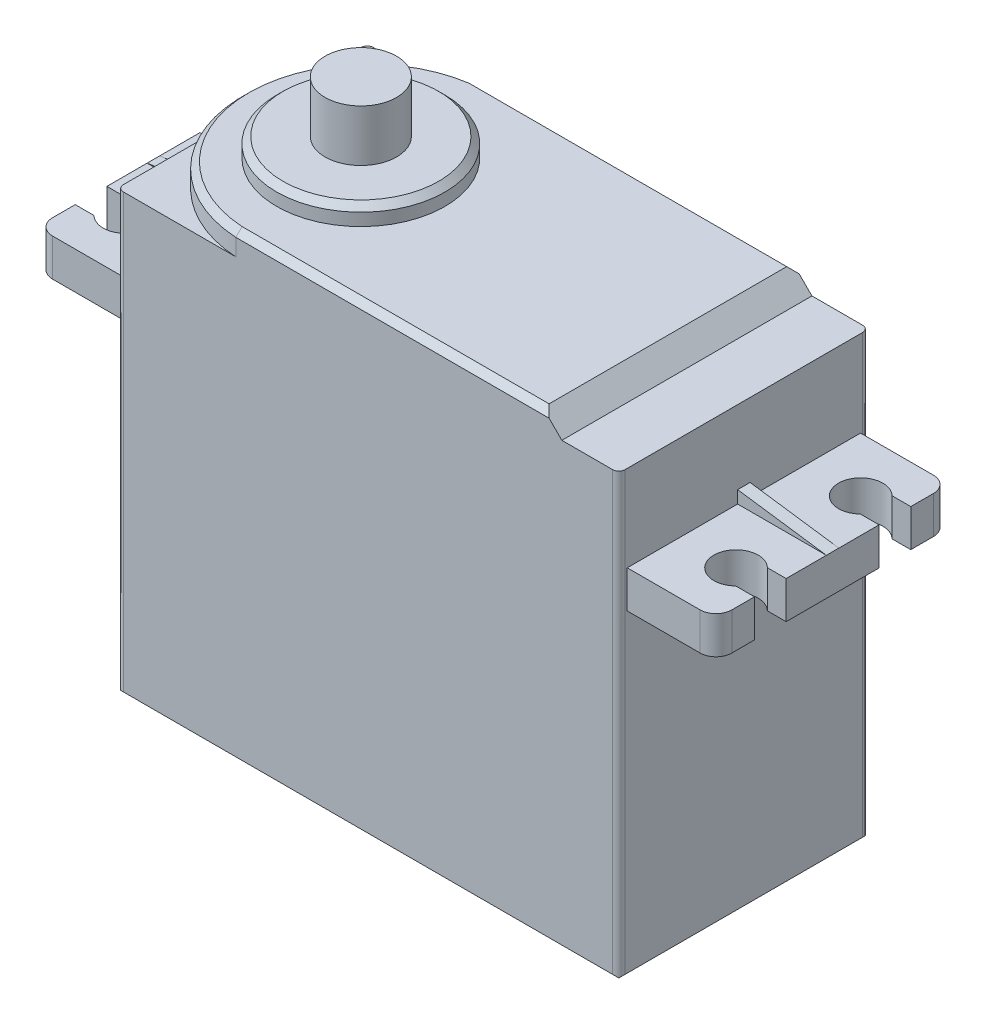
SolidWorks part; units mm, degrees
ref_plane "Front Plane" through (0, 0, 0) normal (0, 0, 1) x (1, 0, 0)
ref_plane "Top Plane" through (0, 0, 0) normal (0, 1, 0) x (1, 0, 0)
ref_plane "Right Plane" through (0, 0, 0) normal (1, 0, 0) x (0, 0, -1)
sketch "Sketch1" plane through (0, 0, 0) normal (0, 1, 0) x (1, 0, 0)
  line L1 (-20.1295, -10.033) -> (20.1295, -10.033)
  line L2 (-20.1295, -10.033) -> (-20.1295, 10.033)
  line L3 (-20.1295, 10.033) -> (20.1295, 10.033)
  line L4 (20.1295, -10.033) -> (20.1295, 10.033)
  line L5 (-20.1295, -10.033) -> (20.1295, 10.033) construction
  line L6 (-20.1295, 10.033) -> (20.1295, -10.033) construction
  point P0 (0, 0)
  dimension "D1" = 20.066
  dimension "D2" = 40.259
extrude "Boss-Extrude1" add sketch "Sketch1" along normal blind 38.1
ref_plane "Plane1" through (0, 26.67, 0) normal (0, -1, 0) x (-1, 0, 0)
sketch "Sketch2" plane through (0, 26.67, 0) normal (0, -1, 0) x (-1, 0, 0)
  line L1 (27.25, -9.3599) -> (-27.25, -9.3599)
  line L2 (27.25, -9.3599) -> (27.25, 9.3599)
  line L3 (27.25, 9.3599) -> (-27.25, 9.3599)
  line L4 (-27.25, -9.3599) -> (-27.25, 9.3599)
  line L5 (27.25, -9.3599) -> (-27.25, 9.3599) construction
  line L6 (27.25, 9.3599) -> (-27.25, -9.3599) construction
  point P0 (0, 0)
  dimension "D1" = 18.7198
  dimension "D2" = 54.5
extrude "Boss-Extrude2" add sketch "Sketch2" against normal blind 2.9972
sketch "Sketch3" plane through (0, 38.1, 0) normal (0, 1, 0) x (1, 0, 0)
  line L0 (-20.1295, 10.033) -> (-20.1295, -10.033) construction
  circle A0 centre (-10.6045, 0) radius 2.8702
  dimension "D2" = 5.7404
  dimension "D1" = 9.525
extrude "Boss-Extrude3" add sketch "Sketch3" along normal blind 5.6388
sketch "Sketch4" plane through (0, 29.6672, 0) normal (0, 1, 0) x (1, 0, 0)
  line L0 (-35.4024, 0) -> (37.6199, 0) construction
  line L1 (0, 17.908) -> (0, -16.6827) construction
  circle A0 centre (-24.5, 5) radius 1.778
  circle A1 centre (-24.5, -5) radius 1.778
  circle A2 centre (24.5, -5) radius 1.778
  circle A3 centre (24.5, 5) radius 1.778
  dimension "D3" = 3.556
  dimension "D4" = 3.556
  dimension "D5" = 3.556
  dimension "D6" = 3.556
  dimension "D1" = 49
  dimension "D2" = 10
extrude "Cut-Extrude1" cut sketch "Sketch4" against normal through all
sketch "Sketch5" plane through (0, 29.6672, 0) normal (0, 1, 0) x (1, 0, 0)
  line L0 (-24.5, -5) -> (-36.94, -5) construction
  line L1 (24.5, 5) -> (34.8628, 5) construction
  line L2 (-24.5, 5) -> (-37.4141, 5) construction
  line L3 (24.5, -5) -> (35.3369, -5) construction
  line L5 (-32.12, 3.73) -> (-24.5, 3.73)
  line L6 (-32.12, 3.73) -> (-32.12, 6.27)
  line L7 (-32.12, 6.27) -> (-24.5, 6.27)
  line L8 (-24.5, 3.73) -> (-24.5, 6.27)
  line L9 (-32.12, 3.73) -> (-24.5, 6.27) construction
  line L10 (-32.12, 6.27) -> (-24.5, 3.73) construction
  line L11 (-30.85, -6.27) -> (-24.5, -6.27)
  line L12 (-30.85, -6.27) -> (-30.85, -3.73)
  line L13 (-30.85, -3.73) -> (-24.5, -3.73)
  line L14 (-24.5, -6.27) -> (-24.5, -3.73)
  line L15 (-30.85, -6.27) -> (-24.5, -3.73) construction
  line L16 (-30.85, -3.73) -> (-24.5, -6.27) construction
  line L17 (30.85, 3.73) -> (24.5, 3.73)
  line L18 (30.85, 3.73) -> (30.85, 6.27)
  line L19 (30.85, 6.27) -> (24.5, 6.27)
  line L20 (24.5, 3.73) -> (24.5, 6.27)
  line L21 (30.85, 3.73) -> (24.5, 6.27) construction
  line L22 (30.85, 6.27) -> (24.5, 3.73) construction
  line L23 (30.85, -6.27) -> (24.5, -6.27)
  line L24 (30.85, -6.27) -> (30.85, -3.73)
  line L25 (30.85, -3.73) -> (24.5, -3.73)
  line L26 (24.5, -6.27) -> (24.5, -3.73)
  line L27 (30.85, -6.27) -> (24.5, -3.73) construction
  line L28 (30.85, -3.73) -> (24.5, -6.27) construction
  point P2 (-28.31, 5)
  point P17 (-27.675, -5)
  point P22 (27.675, 5)
  point P27 (27.675, -5)
  dimension "D1" = 7.62
  dimension "D2" = 6.35
  dimension "D3" = 2.54
  dimension "D4" = 2.54
  dimension "D5" = 6.35
  dimension "D6" = 6.35
  dimension "D7" = 2.54
  dimension "D8" = 2.54
extrude "Cut-Extrude2" cut sketch "Sketch5" against normal through all
fillet "Fillet2" radius 1.27 4 edges at (27.25, 28.1686, -9.3599) (27.25, 28.1686, 9.3599) (-27.25, 28.1686, 9.3599) (-27.25, 28.1686, -9.3599)
sketch "Sketch6" plane through (-20.1295, 0, 0) normal (-1, 0, 0) x (0, 0, 1)
  line L0 (-10.033, 0) -> (10.033, 0) construction
  line L1 (-3.6195, 7.874) -> (3.6195, 7.874)
  line L2 (-3.6195, 7.874) -> (-3.6195, 3.556)
  line L3 (-3.6195, 3.556) -> (3.6195, 3.556)
  line L4 (3.6195, 7.874) -> (3.6195, 3.556)
  line L5 (-3.6195, 7.874) -> (3.6195, 3.556) construction
  line L6 (-3.6195, 3.556) -> (3.6195, 7.874) construction
  line L7 (0, 0) -> (0, 13.3979) construction
  point P0 (0, 5.715)
  dimension "D1" = 3.556
  dimension "D2" = 4.318
  dimension "D3" = 7.239
extrude "Boss-Extrude4" add sketch "Sketch6" along normal blind 5.08 draft 5
sketch "Sketch7" plane through (0, 38.1, 0) normal (0, 1, 0) x (1, 0, 0)
  line L0 (20.1295, 10.033) -> (-20.1295, 10.033) construction
  line L1 (20.1295, -10.033) -> (15.5575, -10.033)
  line L2 (20.1295, -10.033) -> (20.1295, 10.033)
  line L3 (20.1295, 10.033) -> (15.5575, 10.033)
  line L4 (15.5575, -10.033) -> (15.5575, 10.033)
  dimension "D1" = 4.572
extrude "Cut-Extrude3" cut sketch "Sketch7" against normal blind 1.524
chamfer "Chamfer1" distance 1.524 angle 45 1 edges at (15.5575, 38.1, 0)
sketch "Sketch8" plane through (0, 38.1, 0) normal (0, 1, 0) x (1, 0, 0)
  line L0 (-10.6045, 20.2431) -> (-10.6045, 0) construction
  line L1 (-10.6045, 10.1215) -> (-31.4314, 17.8122)
  line L2 (-10.6045, 0) -> (-32.3007, 0) construction
  line L3 (-31.4314, 17.8122) -> (-23.5267, -15.8682)
  line L4 (-10.6045, 0) -> (-10.6045, -17.0893) construction
  line L5 (0, 10.033) -> (-28.1984, 10.033) construction
  line L6 (14.0335, 10.033) -> (-20.1295, 10.033) construction
  line L7 (4.8815, -10.033) -> (-38.0382, -10.033) construction
  line L8 (-20.1295, -10.033) -> (14.0335, -10.033) construction
  line L9 (-20.1295, 10.033) -> (-20.1295, -10.033) construction
  line L10 (-23.5267, -15.8682) -> (-10.6045, -10.033)
  arc A0 (-10.6045, 10.1215) -> (-10.6045, -10.033) centre (-10.0362, 0.0443) ccw
  point P10 (-10.6045, -10.033)
  point P13 (-10.6045, 10.033)
  point P18 (-20.1295, 0)
extrude "Cut-Extrude4" cut sketch "Sketch8" against normal blind 1.8542
sketch "Sketch9" plane through (0, 38.1, 0) normal (0, 1, 0) x (1, 0, 0)
  circle A0 centre (-10.6045, 0) radius 6.75
  dimension "D1" = 13.5
extrude "Boss-Extrude5" add sketch "Sketch9" along normal blind 1.5
chamfer "Chamfer2" distance 0.5 angle 45 4 edges at (1.2742, 38.1, -10.033) (1.7145, 38.1, 10.033) (-20.1198, 38.1, 0.3983) (-10.6045, 39.6, 6.75) tangent propagation no
chamfer "Chamfer3" distance 1.5 angle 45 4 edges at (0, 0, -10.033) (-20.1295, 0, 0) (0, 0, 10.033) (20.1295, 0, 0)
fillet "Fillet3" radius 0.5 4 edges at (-20.1295, 18.8729, -10.033) (-20.1295, 18.8729, 10.033) (20.1295, 19.038, 10.033) (20.1295, 19.038, -10.033)
sketch "Sketch12" plane through (0, 0, 0) normal (0, 0, 1) x (1, 0, 0)
  line L0 (-27.25, 29.6672) -> (-20.1295, 29.6672)
  line L1 (-20.1295, 29.6672) -> (-20.1295, 30.6672)
  line L2 (-20.1295, 1.5) -> (-20.1295, 36.2458) construction
  line L3 (-20.1295, 30.6672) -> (-27.25, 29.6672)
  dimension "D1" = 1
extrude "Boss-Extrude6" add sketch "Sketch12" along normal blind 0.5 and the other way blind 0.5
mirror "Mirror1" about plane through (0, 0, 0) normal (1, 0, 0) of "Boss-Extrude6"
fillet "Fillet4" radius 1 8 edges at (-25.2095, 4.0004, 0) (-25.2095, 5.715, -3.1751) (-25.2095, 7.4296, 0) (-25.2095, 5.715, 3.1751) (-22.6695, 7.6518, -3.3973) (-22.6695, 7.6518, 3.3973) (-22.6695, 3.7782, -3.3973) (-22.6695, 3.7782, 3.3973) tangent propagation no
